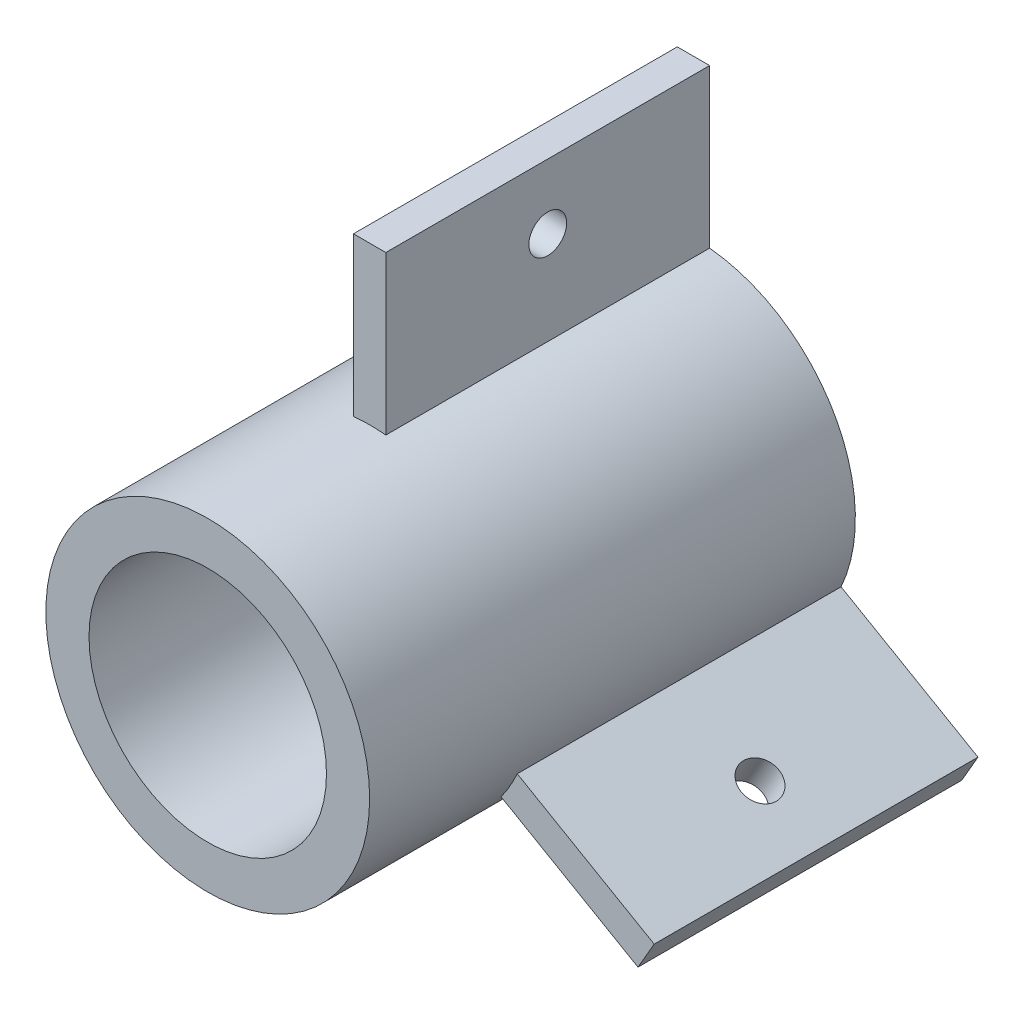
SolidWorks part; units mm, degrees
ref_plane "前基準面" through (0, 0, 0) normal (0, 0, 1) x (1, 0, 0)
ref_plane "上基準面" through (0, 0, 0) normal (0, 1, 0) x (1, 0, 0)
ref_plane "右基準面" through (0, 0, 0) normal (1, 0, 0) x (0, 0, -1)
sketch "草圖1" plane through (0, 0, 0) normal (0, 0, 1) x (1, 0, 0)
  circle A0 centre (0, 0) radius 15
  dimension "D1" = 30
extrude "填料-伸長1" add sketch "草圖1" along normal blind 45
sketch "草圖2" plane through (0, 0, 45) normal (0, 0, 1) x (1, 0, 0)
  circle A0 centre (0, 0) radius 11
  dimension "D1" = 22
extrude "除料-伸長1" cut sketch "草圖2" against normal blind 40
sketch "草圖3" plane through (0, 0, 5) normal (0, 0, 1) x (1, 0, 0)
  circle A0 centre (0, 0) radius 7.5
  dimension "D1" = 15
extrude "除料-伸長2" cut sketch "草圖3" against normal blind 5
sketch "草圖4" plane through (0, 0, 0) normal (0, 0, 1) x (1, 0, 0)
  line L0 (26.361, -13.4875) -> (13.3706, -5.9875)
  line L1 (-1.5, 29.5731) -> (1.5, 29.5731)
  line L2 (-1.5, 29.5731) -> (-1.5, 14.5731)
  line L3 (-1.5, 14.5731) -> (1.5, 14.5731)
  line L4 (1.5, 29.5731) -> (1.5, 14.5731)
  line L5 (26.361, -13.4875) -> (24.861, -16.0856)
  line L6 (24.861, -16.0856) -> (11.8706, -8.5856)
  line L7 (13.3706, -5.9875) -> (11.8706, -8.5856)
  line L8 (-24.861, -16.0856) -> (-11.8706, -8.5856)
  line L9 (-24.861, -16.0856) -> (-26.361, -13.4875)
  line L10 (-26.361, -13.4875) -> (-13.3706, -5.9875)
  line L11 (-11.8706, -8.5856) -> (-13.3706, -5.9875)
  point P4 (0, 14.5731)
  point P6 (28.2848, 9.0942)
  point P17 (0, 0)
  dimension "D1" = 15
  dimension "D2" = 3
  dimension "D3" = 14.5731
  dimension "D4" = 3
extrude "填料-伸長2" add sketch "草圖4" along normal blind 30
sketch "草圖5" plane through (-0.75, -1.299, 0) normal (-0.5, -0.866, 0) x (0.866, -0.5, 0)
  line L0 (29.5731, 30) -> (29.5731, 0) construction
  circle A0 centre (23.5731, 15) radius 1.75
  point P4 (29.5731, 15)
  dimension "D1" = 3.5
  dimension "D2" = 6
extrude "除料-伸長3" cut sketch "草圖5" against normal blind 30
sketch "草圖6" plane through (1.5, 0, 0) normal (1, 0, 0) x (0, 0, -1)
  line L0 (-30, 29.5731) -> (0, 29.5731) construction
  circle A0 centre (-15, 23.5731) radius 1.75
  point P4 (0, 0)
  point P5 (-14.0842, 23.5731)
  point P6 (-15, 29.5731)
  dimension "D1" = 3.5
  dimension "D2" = 6
extrude "除料-伸長4" cut sketch "草圖6" against normal blind 30
sketch "草圖7" plane through (-0.75, 1.299, 0) normal (-0.5, 0.866, 0) x (0.866, 0.5, 0)
  line L0 (-29.5731, -30) -> (-29.5731, 0) construction
  circle A0 centre (-23.5731, -15) radius 1.75
  point P4 (-29.5731, -15)
  dimension "D1" = 3.5
  dimension "D2" = 6
extrude "除料-伸長5" cut sketch "草圖7" against normal blind 30
